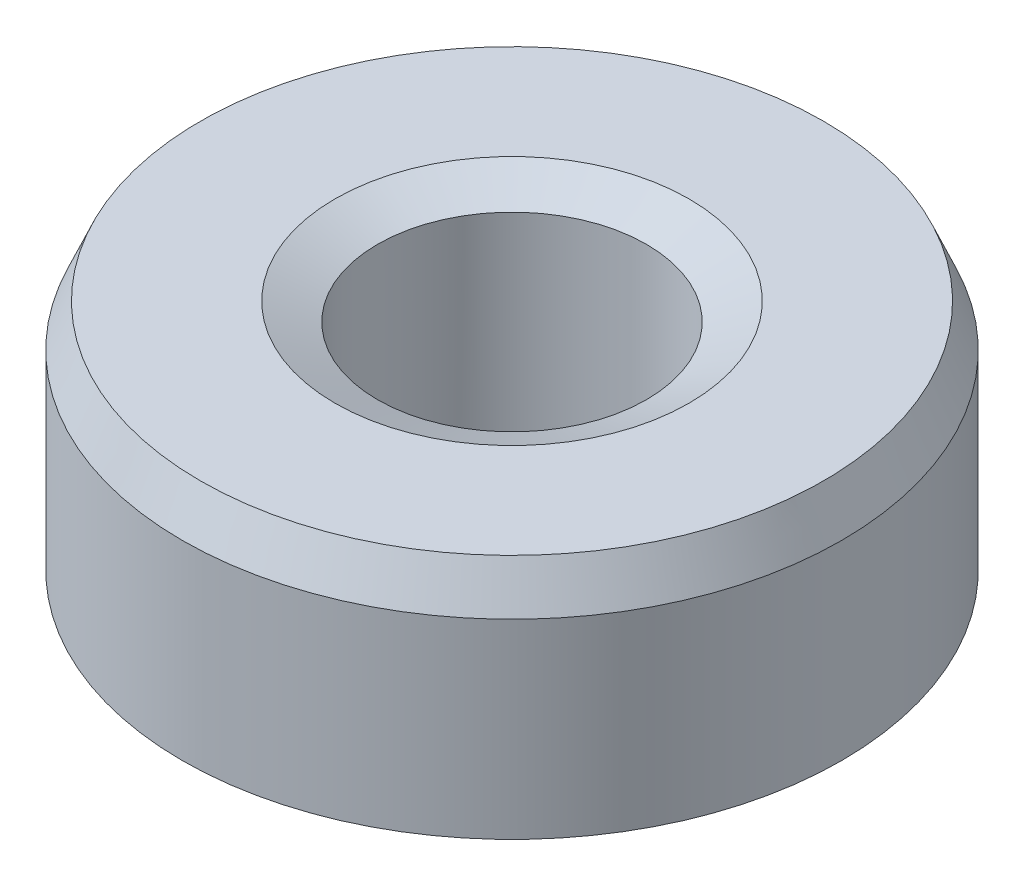
SolidWorks part; units mm, degrees
ref_plane "Front Plane" through (0, 0, 0) normal (0, 0, 1) x (1, 0, 0)
ref_plane "Top Plane" through (0, 0, 0) normal (0, 1, 0) x (1, 0, 0)
ref_plane "Right Plane" through (0, 0, 0) normal (1, 0, 0) x (0, 0, -1)
sketch "Sketch1" plane through (0, 0, 0) normal (0, 1, 0) x (1, 0, 0)
  circle A0 centre (0, 0) radius 7.5
  dimension "SLEEVE_OD" = 15
extrude "Boss-Extrude1" add sketch "Sketch1" along normal blind 5.7166
sketch "Sketch2" plane through (0, 0, 0) normal (0, 1, 0) x (1, 0, 0)
  circle A0 centre (0, 0) radius 3.0606
  dimension "BORE_D" = 6.1211
extrude "Cut-Extrude1" cut sketch "Sketch2" along normal through all
chamfer "Chamfer1" distance 0.9661 angle 23.14 4 edges at (0, 5.7166, 3.0606) (0, 0, 3.0606) (0, 0, 7.5) (0, 5.7166, 7.5) first distance on face at (0, 5.7166, 3.0606) first distance on face at (0, 0, 3.0606) first distance on face at (0, 5.7166, 7.5)
